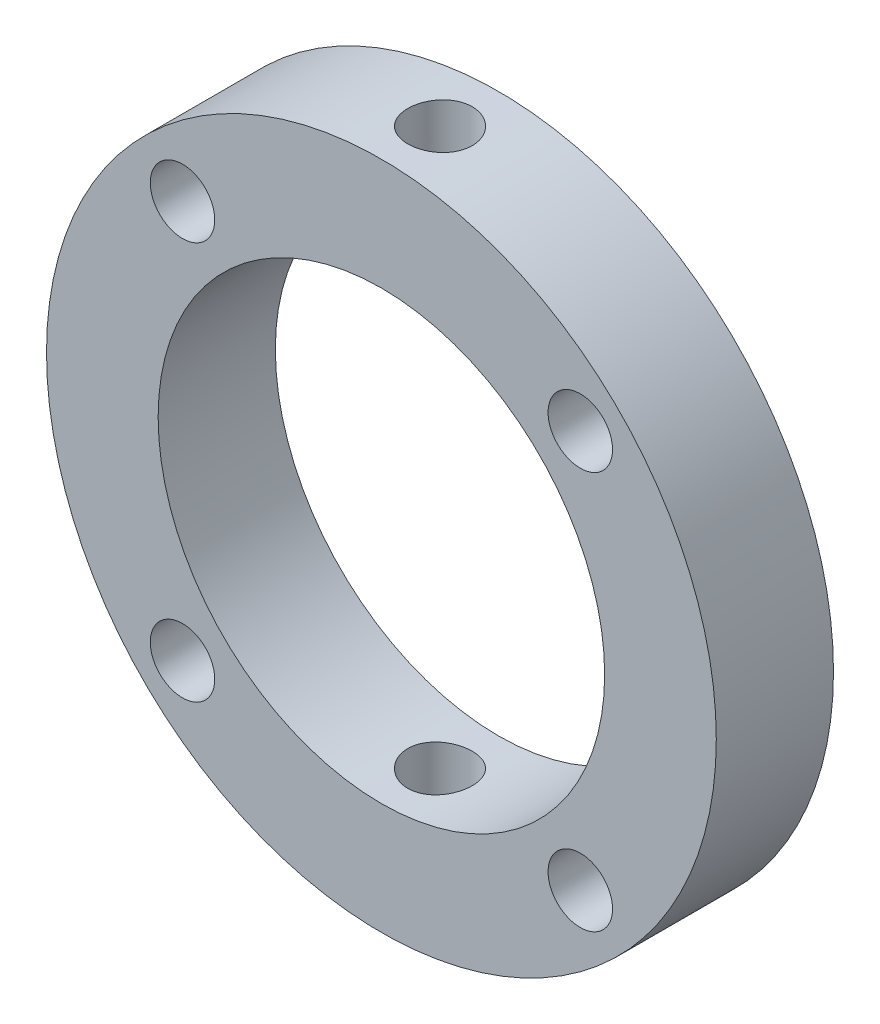
SolidWorks part; units mm, degrees
ref_plane "Front Plane" through (0, 0, 0) normal (0, 0, 1) x (1, 0, 0)
ref_plane "Top Plane" through (0, 0, 0) normal (0, 1, 0) x (1, 0, 0)
ref_plane "Right Plane" through (0, 0, 0) normal (1, 0, 0) x (0, 0, -1)
sketch "Sketch1" plane through (0, 0, 0) normal (0, 0, 1) x (1, 0, 0)
  circle A0 centre (0, 0) radius 28.575
  dimension "D1" = 57.15
extrude "Boss-Extrude1" add sketch "Sketch1" along normal blind 10
sketch "Sketch2" plane through (0, 0, 10) normal (0, 0, 1) x (1, 0, 0)
  circle A0 centre (0, 0) radius 19.05
  dimension "D1" = 38.1
extrude "Cut-Extrude1" cut sketch "Sketch2" against normal through all
ref_plane "Plane1" through (0, 28.575, 0) normal (0, 1, 0) x (1, 0, 0)
sketch "Sketch5" plane through (0, 28.575, 0) normal (0, 1, 0) x (1, 0, 0)
  circle A0 centre (0, -5) radius 2.75
  dimension "D2" = 5.5
  dimension "D1" = 5
extrude "Cut-Extrude2" cut sketch "Sketch5" against normal through all
sketch "Sketch6" plane through (0, 0, 10) normal (0, 0, 1) x (1, 0, 0)
  line L0 (0, 28.575) -> (0, -28.575) construction
  line L1 (5.5, 28.575) -> (-5.5, 28.575) construction
  line L2 (-16.9706, 16.9706) -> (0, 0) construction
  circle A0 centre (-16.9706, 16.9706) radius 2.75
  circle A1 centre (0, 0) radius 28.575 construction
  circle A3 centre (16.9706, 16.9706) radius 2.75
  circle A4 centre (16.9706, -16.9706) radius 2.75
  circle A5 centre (-16.9706, -16.9706) radius 2.75
  point P9 (0, 0)
  point P11 (0, 0)
  point P19 (0, 0)
  point P20 (20.2361, 8.7097)
  point P21 (0, 0)
  dimension "D2" = 5.5
  dimension "D1" = 24
  dimension "D4" = 45
  dimension "D3" = 4
extrude "Cut-Extrude3" cut sketch "Sketch6" against normal through all
